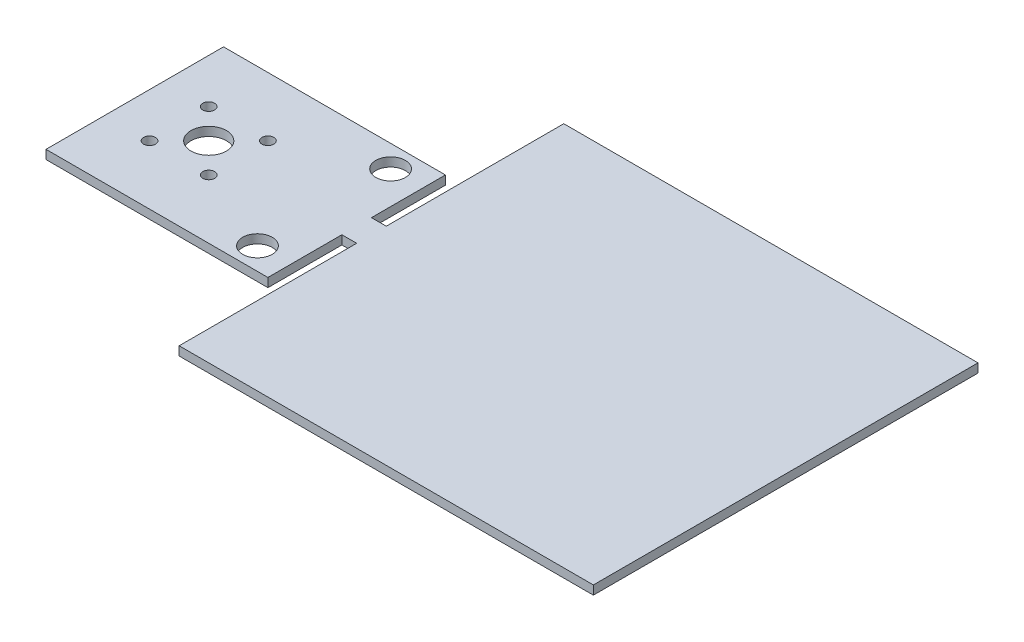
SolidWorks part; units mm, degrees
ref_plane "Front" through (0, 0, 0) normal (0, 0, 1) x (1, 0, 0)
ref_plane "Top" through (0, 0, 0) normal (0, 1, 0) x (1, 0, 0)
ref_plane "Right" through (0, 0, 0) normal (1, 0, 0) x (0, 0, -1)
sketch "Sketch1" plane through (0, 0, 0) normal (0, 1, 0) x (1, 0, 0)
  line L0 (70, 65) -> (70, 5)
  line L1 (-74, -77.5) -> (74, -77.5) construction
  line L2 (-74, -77.5) -> (-74, 77.5) construction
  line L3 (-74, 77.5) -> (74, 77.5) construction
  line L4 (74, -77.5) -> (74, 77.5) construction
  line L5 (-74, -77.5) -> (74, 77.5) construction
  line L6 (-74, 77.5) -> (74, -77.5) construction
  line L7 (-70, -65) -> (70, -65)
  line L8 (-150, -30) -> (-150, 30)
  line L9 (-70, 65) -> (70, 65)
  line L10 (150, -30) -> (150, 30)
  line L11 (0, 0) -> (45.3673, 0) construction
  line L12 (0, 0) -> (0, 51.3703) construction
  line L13 (75, 30) -> (150, 30)
  line L14 (-75, 30) -> (-150, 30)
  line L15 (-70, 65) -> (-70, 5)
  line L16 (70, -65) -> (70, -5)
  line L17 (-70, -65) -> (-70, -5)
  line L18 (-75, -30) -> (-150, -30)
  line L19 (75, -30) -> (150, -30)
  line L20 (125, 0) -> (125, 16.6657) construction
  line L21 (75, 30) -> (75, 5)
  line L22 (75, 5) -> (70, 5)
  line L24 (75, -30) -> (75, -5)
  line L25 (75, -5) -> (70, -5)
  line L26 (-75, -30) -> (-75, -5)
  line L27 (-75, -5) -> (-70, -5)
  line L28 (-75, 30) -> (-75, 5)
  line L29 (-75, 5) -> (-70, 5)
  circle A0 centre (125, 0) radius 6
  circle A1 centre (115, 10) radius 2
  circle A2 centre (135, 10) radius 2
  circle A3 centre (135, -10) radius 2
  circle A4 centre (115, -10) radius 2
  circle A5 centre (-115, -10) radius 2
  circle A6 centre (-135, -10) radius 2
  circle A7 centre (-135, 10) radius 2
  circle A8 centre (-125, 0) radius 6
  circle A9 centre (-115, 10) radius 2
  circle A10 centre (100, 0) radius 7.5
  circle A11 centre (-100, 0) radius 7.5
  point P0 (0, 0)
  point P6 (0, 0)
  dimension "D9" = 15
  dimension "D10" = 4
  dimension "D11" = 12
  dimension "D1" = 148
  dimension "D2" = 155
  dimension "D3" = 140
  dimension "D4" = 130
  dimension "D5" = 60
  dimension "D6" = 300
  dimension "D7" = 250
  dimension "D8" = 200
  dimension "D12" = 5
  dimension "D13" = 10
extrude "Boss-Extrude1" add sketch "Sketch1" along normal mid plane 3
sketch "Sketch2" plane through (0, 1.5, 0) normal (0, 1, 0) x (1, 0, 0)
  line L1 (70, 65) -> (185.2196, 65)
  line L2 (70, 65) -> (70, -80.3443)
  line L3 (70, -80.3443) -> (185.2196, -80.3443)
  line L4 (185.2196, 65) -> (185.2196, -80.3443)
extrude "Cut-Extrude1" cut sketch "Sketch2" against normal through all
sketch "Sketch3" plane through (0, 1.5, 0) normal (0, 1, 0) x (1, 0, 0)
  line L0 (-125, 0) -> (-86.0289, 22.5)
  line L1 (-86.0289, 22.5) -> (-86.0289, -22.5)
  line L2 (-86.0289, -22.5) -> (-125, 0)
  dimension "D1" = 38.9711
  dimension "D2" = 45
other "DeleteFace1" face at (-100, 1.5, -7.5) and patch yes
sketch "Sketch4" plane through (0, 1.5, 0) normal (0, 1, 0) x (1, 0, 0)
  line L0 (-125, 0) -> (-81.6733, 0) construction
  circle A0 centre (-86.0289, -22.5) radius 5
  circle A1 centre (-86.0289, 22.5) radius 5
  dimension "D1" = 10
extrude "Cut-Extrude2" cut sketch "Sketch4" against normal through all
